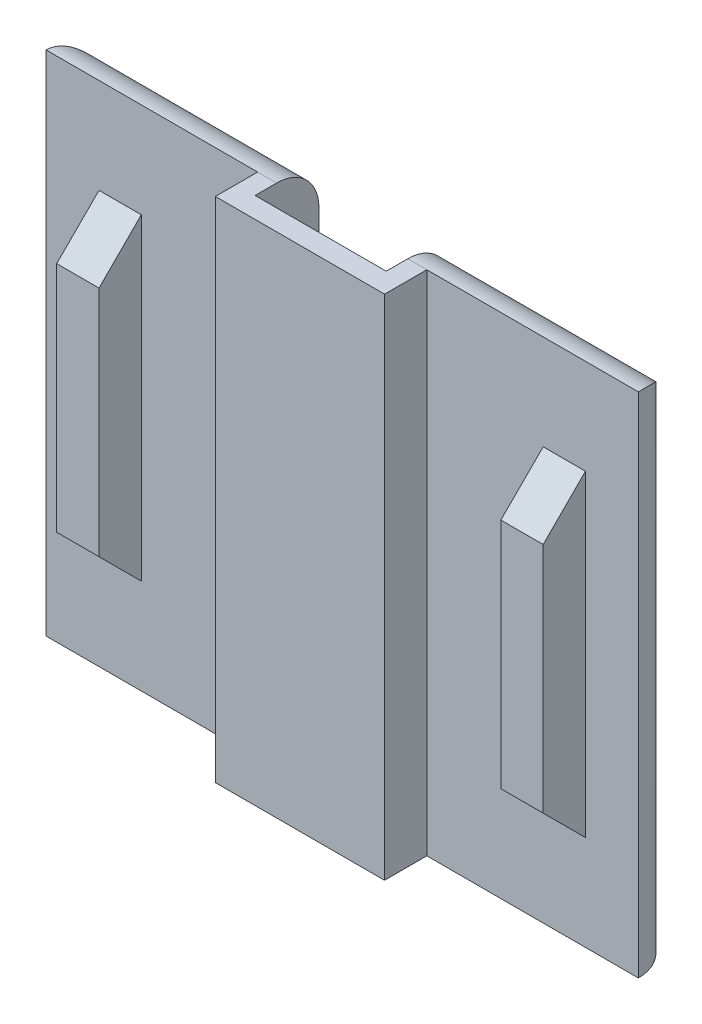
SolidWorks part; units mm, degrees
ref_plane "Front Plane" through (0, 0, 0) normal (0, 0, 1) x (1, 0, 0)
ref_plane "Top Plane" through (0, 0, 0) normal (0, 1, 0) x (1, 0, 0)
ref_plane "Right Plane" through (0, 0, 0) normal (1, 0, 0) x (0, 0, -1)
sketch "Sketch1" plane through (0, 0, 0) normal (0, 0, 1) x (1, 0, 0)
  line L1 (7, -6) -> (-7, -6)
  line L2 (7, -6) -> (7, 6)
  line L3 (7, 6) -> (-7, 6)
  line L4 (-7, -6) -> (-7, 6)
  line L5 (7, -6) -> (-7, 6) construction
  line L6 (7, 6) -> (-7, -6) construction
  point P0 (0, 0)
  dimension "D1" = 14
  dimension "D2" = 12
extrude "Boss-Extrude1" add sketch "Sketch1" along normal blind 1
sketch "Sketch2" plane through (0, 0, 1) normal (0, 0, 1) x (1, 0, 0)
  line L0 (7, 6) -> (-7, 6) construction
  line L1 (-2, -6) -> (2, -6)
  line L2 (-2, -6) -> (-2, 6)
  line L3 (-2, 6) -> (2, 6)
  line L4 (2, -6) -> (2, 6)
  line L5 (-2, -6) -> (2, 6) construction
  line L6 (-2, 6) -> (2, -6) construction
  point P0 (0, 0)
  dimension "D1" = 4
extrude "Boss-Extrude2" add sketch "Sketch2" along normal blind 1
sketch "Sketch3" plane through (0, 6, 0) normal (0, 1, 0) x (1, 0, 0)
  line L0 (7, 0) -> (-7, 0) construction
  line L1 (-1.55, 0) -> (1.55, 0)
  line L2 (-1.55, 0) -> (-1.55, -1.51)
  line L3 (-1.55, -1.51) -> (1.55, -1.51)
  line L4 (1.55, 0) -> (1.55, -1.51)
  line L5 (-2, -2) -> (-2, -1) construction
  line L6 (2, -2) -> (2, -1) construction
  point P8 (2, -1.5)
  dimension "D1" = 3.1
  dimension "D2" = 0.45
  dimension "D3" = 0.45
  dimension "D4" = 1.51
extrude "Cut-Extrude1" cut sketch "Sketch3" against normal through all
sketch "Sketch5" plane through (0, 0, 1) normal (0, 0, 1) x (1, 0, 0)
  line L0 (-7, 6) -> (-7, -6) construction
  line L1 (5.75, -4.75) -> (-5.75, -4.75)
  line L2 (5.75, -4.75) -> (5.75, 4.75)
  line L3 (5.75, 4.75) -> (-5.75, 4.75)
  line L4 (-5.75, -4.75) -> (-5.75, 4.75)
  line L5 (5.75, -4.75) -> (-5.75, 4.75) construction
  line L6 (5.75, 4.75) -> (-5.75, -4.75) construction
  line L7 (-2, 6) -> (-7, 6) construction
  point P0 (0, 0)
  dimension "D1" = 1.25
  dimension "D2" = 1.25
sketch "Sketch6" plane through (0, 0, 1) normal (0, 0, 1) x (1, 0, 0)
  line L0 (5.75, 4.75) -> (-5.75, 4.75) construction
  line L1 (5.75, -4.75) -> (4.75, -4.75)
  line L2 (5.75, -4.75) -> (5.75, 4.75)
  line L3 (5.75, 4.75) -> (4.75, 4.75)
  line L4 (4.75, -4.75) -> (4.75, 4.75)
  line L5 (5.75, -4.75) -> (-5.75, -4.75) construction
  line L6 (-5.75, 4.75) -> (-4.75, 4.75)
  line L7 (-5.75, 4.75) -> (-5.75, -4.75)
  line L8 (-5.75, -4.75) -> (-4.75, -4.75)
  line L9 (-4.75, 4.75) -> (-4.75, -4.75)
  dimension "D1" = 1
  dimension "D2" = 1
extrude "Boss-Extrude5" add sketch "Sketch6" along normal blind 1
fillet "Fillet2" radius 1 4 edges at (-4.275, 6, 0) (4.275, 6, 0) (7, 0, 0) (-7, 0, 0)
sketch "Sketch7" plane through (0, 0, 2) normal (0, 0, 1) x (1, 0, 0)
  line L0 (-4.75, -4.75) -> (-4.75, 4.75) construction
  line L1 (-5.75, -4.75) -> (-4.75, -4.75)
  line L2 (-5.75, -4.75) -> (-5.75, -3.75)
  line L3 (-5.75, -3.75) -> (-4.75, -3.75)
  line L4 (-4.75, -4.75) -> (-4.75, -3.75)
  line L5 (5.75, -4.75) -> (5.75, 4.75) construction
  line L6 (4.75, -4.75) -> (5.75, -4.75)
  line L7 (4.75, -4.75) -> (4.75, -3.75)
  line L8 (4.75, -3.75) -> (5.75, -3.75)
  line L9 (5.75, -4.75) -> (5.75, -3.75)
  line L11 (-5.75, 4.75) -> (-4.75, 4.75)
  line L12 (-5.75, 4.75) -> (-5.75, 3.75)
  line L13 (-5.75, 3.75) -> (-4.75, 3.75)
  line L14 (-4.75, 4.75) -> (-4.75, 3.75)
  line L15 (4.75, 4.75) -> (5.75, 4.75)
  line L16 (4.75, 4.75) -> (4.75, 3.75)
  line L17 (4.75, 3.75) -> (5.75, 3.75)
  line L18 (5.75, 4.75) -> (5.75, 3.75)
  dimension "D1" = 1
  dimension "D2" = 1
  dimension "D3" = 1
  dimension "D4" = 1
extrude "Cut-Extrude2" cut sketch "Sketch7" against normal up to surface (1 mm away) up to face at (-4.5, 1.5, 1)
chamfer "Chamfer1" distance 1 angle 45 4 edges at (5.25, -3.75, 2) (-5.25, -3.75, 2) (5.25, 3.75, 2) (-5.25, 3.75, 2)
